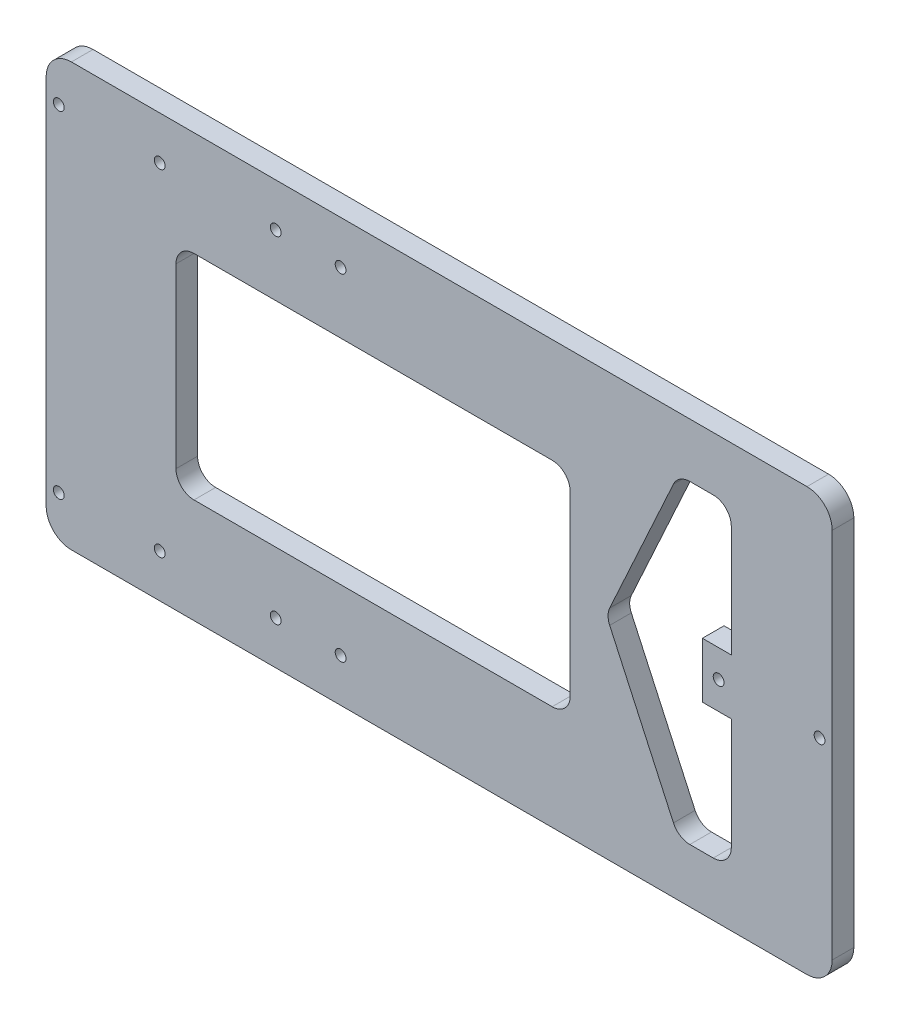
SolidWorks part; units mm, degrees
ref_plane "Front Plane" through (0, 0, 0) normal (0, 0, 1) x (1, 0, 0)
ref_plane "Top Plane" through (0, 0, 0) normal (0, 1, 0) x (1, 0, 0)
ref_plane "Right Plane" through (0, 0, 0) normal (1, 0, 0) x (0, 0, -1)
sketch "Sketch1" plane through (0, 0, 0) normal (0, 0, 1) x (1, 0, 0)
  line L0 (-242.1092, 256.3436) -> (-242.1092, 139.1436) construction
  line L1 (-59.1092, 256.3436) -> (-59.1092, 139.1436) construction
  line L2 (-242.1092, 139.1436) -> (-59.1092, 139.1436) construction
  line L3 (-150.6092, 256.3436) -> (-150.6092, 306.7436) construction
  line L4 (-238.1092, 139.1436) -> (-246.1092, 139.1436) construction
  line L5 (-242.1092, 256.3436) -> (-59.1092, 256.3436) construction
  line L6 (-238.1092, 139.1436) -> (-238.1092, 256.3436) construction
  line L7 (-238.1092, 256.3436) -> (-246.1092, 256.3436) construction
  line L8 (-246.1092, 139.1436) -> (-246.1092, 256.3436) construction
  line L9 (-238.1092, 139.1436) -> (-246.1092, 256.3436) construction
  line L10 (-238.1092, 256.3436) -> (-246.1092, 139.1436) construction
  line L11 (-55.1092, 139.1436) -> (-63.1092, 139.1436) construction
  line L12 (-55.1092, 139.1436) -> (-55.1092, 256.3436) construction
  line L13 (-55.1092, 256.3436) -> (-63.1092, 256.3436) construction
  line L14 (-63.1092, 139.1436) -> (-63.1092, 256.3436) construction
  line L15 (-55.1092, 139.1436) -> (-63.1092, 256.3436) construction
  line L16 (-55.1092, 256.3436) -> (-63.1092, 139.1436) construction
  line L17 (-231.6092, 232.3436) -> (-252.6092, 232.3436)
  line L18 (-231.6092, 232.3436) -> (-231.6092, 256.3436)
  line L19 (-231.6092, 256.3436) -> (-252.6092, 256.3436)
  line L20 (-252.6092, 232.3436) -> (-252.6092, 256.3436)
  line L21 (-231.6092, 232.3436) -> (-252.6092, 256.3436) construction
  line L22 (-231.6092, 256.3436) -> (-252.6092, 232.3436) construction
  line L23 (-252.6092, 163.1436) -> (-231.6092, 163.1436)
  line L24 (-252.6092, 163.1436) -> (-252.6092, 139.1436)
  line L25 (-252.6092, 139.1436) -> (-231.6092, 139.1436)
  line L26 (-231.6092, 163.1436) -> (-231.6092, 139.1436)
  line L27 (-252.6092, 163.1436) -> (-231.6092, 139.1436) construction
  line L28 (-252.6092, 139.1436) -> (-231.6092, 163.1436) construction
  line L29 (-48.6092, 185.7436) -> (-69.6092, 185.7436) construction
  line L30 (-48.6092, 185.7436) -> (-48.6092, 209.7436) construction
  line L31 (-48.6092, 209.7436) -> (-69.6092, 209.7436) construction
  line L32 (-69.6092, 185.7436) -> (-69.6092, 209.7436) construction
  line L33 (-48.6092, 185.7436) -> (-69.6092, 209.7436) construction
  line L34 (-48.6092, 209.7436) -> (-69.6092, 185.7436) construction
  line L35 (-150.6092, 306.7436) -> (-259.6092, 306.7436) construction
  line L37 (-259.6092, 256.3436) -> (-41.6092, 256.3436)
  line L38 (-259.6092, 306.7436) -> (-41.6092, 306.7436)
  line L39 (-259.6092, 306.7436) -> (-259.6092, 88.7436)
  line L40 (-259.6092, 88.7436) -> (-41.6092, 88.7436)
  line L41 (-41.6092, 306.7436) -> (-41.6092, 88.7436)
  line L42 (-259.6092, 256.3436) -> (-259.6092, 139.1436)
  line L43 (-259.6092, 139.1436) -> (-41.6092, 139.1436)
  line L44 (-41.6092, 256.3436) -> (-41.6092, 139.1436)
  circle A0 centre (-269.6092, 244.3436) radius 2.5
  circle A1 centre (-31.6092, 197.7436) radius 2.5
  circle A3 centre (-269.6092, 151.1436) radius 2.5
  circle A6 centre (-256.1092, 244.3436) radius 1.5
  circle A7 centre (-256.1092, 151.1436) radius 1.5
  circle A8 centre (-45.1092, 197.7436) radius 1.5
  circle A9 centre (-73.1092, 197.7436) radius 1.5
  circle A10 centre (-228.1092, 244.3436) radius 1.5
  circle A11 centre (-228.1092, 151.1436) radius 1.5
  point P0 (-242.1092, 197.7436)
  point P9 (-59.1092, 197.7436)
  point P14 (-242.1092, 244.3436)
  point P19 (-242.1092, 151.1436)
  point P24 (-59.1092, 197.7436)
  point P34 (-150.6092, 197.7436)
  dimension "D11" = 5
  dimension "D12" = 10
  dimension "D15" = 3
  dimension "D20" = 5
  dimension "D21" = 10
  dimension "D22" = 5
  dimension "D23" = 3.5
  dimension "D24" = 3.5
  dimension "D1" = 183
  dimension "D2" = 8
  dimension "D3" = 8
  dimension "D4" = 21
  dimension "D5" = 24
  dimension "D6" = 117.2
  dimension "D7" = 21
  dimension "D8" = 24
  dimension "D9" = 21
  dimension "D10" = 24
  dimension "D16" = 109
  dimension "D17" = 109
  dimension "D18" = 218
  dimension "D19" = 218
extrude "Boss-Extrude1" add sketch "Sketch1" along normal blind 6 contours A6 | A10 | A11 | A8 | A9 | L37 L44 L43 L42 | A7 region at (-256.1092, 244.3436, 0) region at (-45.1092, 197.7436, 0) region at (-73.1092, 197.7436, 0) region at (-228.1092, 244.3436, 0) region at (-228.1092, 151.1436, 0)
sketch "Sketch2" plane through (0, 0, 6) normal (0, 0, 1) x (1, 0, 0)
  line L0 (-259.6092, 256.3436) -> (-41.6092, 256.3436) construction
  line L1 (-259.6092, 256.3436) -> (-41.6092, 256.3436)
  line L2 (-186.9425, 273.3122) -> (-186.9425, 128.0805) construction
  line L3 (-259.6092, 256.3436) -> (-259.6092, 139.1436) construction
  line L4 (-256.1092, 244.3436) -> (-152.9234, 244.3436) construction
  line L5 (-256.1092, 151.1436) -> (-151.5972, 151.1436) construction
  circle A1 centre (-195.9425, 151.1436) radius 1.5
  circle A2 centre (-177.9425, 151.1436) radius 1.5
  circle A3 centre (-195.9425, 244.3436) radius 1.5
  circle A4 centre (-177.9425, 244.3436) radius 1.5
  dimension "D2" = 9
  dimension "D3" = 3
  dimension "D4" = 9
  dimension "D5" = 9
  dimension "D6" = 9
  dimension "D1" = 72.6667
extrude "Cut-Extrude1" cut sketch "Sketch2" against normal blind 6 contours A1 | A2 | A3 | A4 region at (-195.9425, 151.1436, 6) region at (-177.9425, 151.1436, 6)
fillet "Fillet1" radius 7 4 edges at (-41.6092, 139.1436, 3) (-41.6092, 256.3436, 3) (-259.6092, 139.1436, 3) (-259.6092, 256.3436, 3)
sketch "Sketch3" plane through (0, 0, 0) normal (0, 0, -1) x (-1, 0, 0)
  line L0 (223.6092, 227.3436) -> (223.6092, 168.1436)
  line L1 (223.6092, 227.3436) -> (114.2758, 227.3436)
  line L2 (114.2758, 227.3436) -> (114.2758, 168.1436)
  line L3 (114.2758, 168.1436) -> (223.6092, 168.1436)
  line L5 (231.6092, 232.3436) -> (235.6283, 232.3436) construction
  line L6 (249.6092, 163.1436) -> (234.6092, 163.1436) construction
  line L7 (41.6092, 249.3436) -> (41.6092, 146.1436) construction
  dimension "D1" = 5
  dimension "D2" = 5
  dimension "D3" = 72.6667
extrude "Cut-Extrude2" cut sketch "Sketch3" against normal blind 10
fillet "Fillet3" radius 5 4 edges at (-114.2758, 168.1436, 3) (-223.6092, 168.1436, 3) (-223.6092, 227.3436, 3) (-114.2758, 227.3436, 3)
sketch "Sketch4" plane through (0, 0, 0) normal (0, 0, -1) x (-1, 0, 0)
  line L0 (84.299, 241.3436) -> (69.5973, 241.3436)
  line L1 (69.5973, 205.4186) -> (69.5973, 241.3436)
  line L2 (69.5973, 205.4186) -> (77.6092, 205.4186)
  line L3 (77.6092, 205.4186) -> (77.6092, 190.0686)
  line L4 (77.6092, 190.0686) -> (69.5973, 190.0686)
  line L5 (69.5973, 190.0686) -> (69.5973, 154.1436)
  line L6 (69.5973, 154.1436) -> (84.299, 154.1436)
  line L7 (84.299, 154.1436) -> (104.2758, 197.7436)
  line L8 (104.2758, 197.7436) -> (84.299, 241.3436)
  line L9 (252.6092, 256.3436) -> (48.6092, 256.3436) construction
  line L10 (252.6092, 139.1436) -> (48.6092, 139.1436) construction
  line L11 (114.2758, 222.3436) -> (114.2758, 173.1436) construction
  dimension "D1" = 15
  dimension "D2" = 15
  dimension "D3" = 10
extrude "Cut-Extrude3" cut sketch "Sketch4" against normal blind 10
fillet "Fillet4" radius 5 5 edges at (-69.5973, 154.1436, 3) (-84.299, 154.1436, 3) (-104.2758, 197.7436, 3) (-84.299, 241.3436, 3) (-69.5973, 241.3436, 3)
